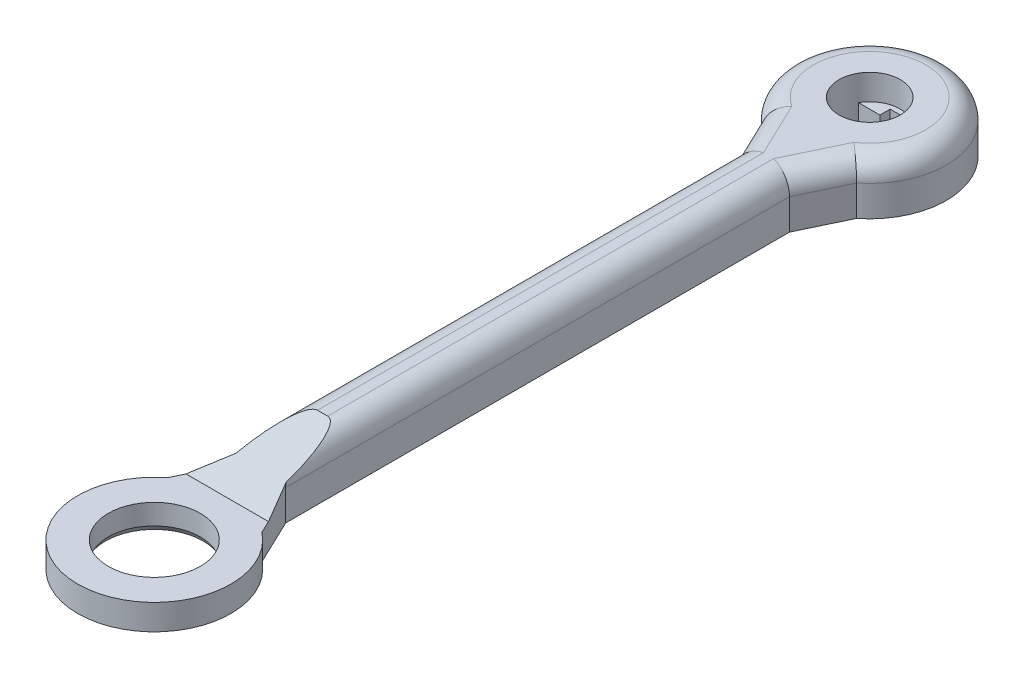
SolidWorks part; units mm, degrees
ref_plane "Front Plane" through (0, 0, 0) normal (0, 0, 1) x (1, 0, 0)
ref_plane "Top Plane" through (0, 0, 0) normal (0, 1, 0) x (1, 0, 0)
ref_plane "Right Plane" through (0, 0, 0) normal (1, 0, 0) x (0, 0, -1)
sketch "Sketch1" plane through (0, 0, 0) normal (0, 1, 0) x (1, 0, 0)
  line L0 (-2.5, 35) -> (-2.5, 0)
  line L1 (-2.5, 35) -> (2.5, 35)
  line L2 (-2.5, 0) -> (2.5, 0)
  line L3 (2.5, 35) -> (2.5, 0)
  line L4 (-2.5, 35) -> (2.5, 0) construction
  line L5 (-2.5, 0) -> (2.5, 35) construction
  circle A0 centre (0, 35) radius 7.5
  point P1 (0, 17.5)
  dimension "D1" = 15
  dimension "D2" = 35
  dimension "D3" = 5
  dimension "D4" = 35
  dimension "D5" = 2.5
extrude "Boss-Extrude1" add sketch "Sketch1" along normal blind 5 contours A0 L0 L2 L3 | L3 A0 L0 L1 | L0 A0 L3 L1 region at (0, 0, -31.3195) region at (0, 0, -35.9678) region at (0, 0, -13.8209)
mirror "Mirror1" about plane through (0, 0, 0) normal (0, 0, 1) of "Boss-Extrude1"
sketch "Sketch2" plane through (0, 0, 0) normal (0, 1, 0) x (1, 0, 0)
  circle A0 centre (0, -35) radius 4.5
  circle A1 centre (0, 35) radius 3
  dimension "D1" = 9
  dimension "D2" = 6
extrude "Cut-Extrude1" cut sketch "Sketch2" along normal blind 5
chamfer "Chamfer3" distance 2 angle 45 4 edges at (-2.5, 2.5, -27.9289) (2.5, 2.5, -27.9289) (-2.5, 2.5, 27.9289) (2.5, 2.5, 27.9289) first distance on face at (0, 2.5, -35.2145) first distance on face at (0, 2.5, 35.2145)
sketch "Sketch4" plane through (0, 5, 0) normal (0, 1, 0) x (1, 0, 0)
  line L1 (8, -27.8664) -> (-8, -27.8664)
  line L2 (8, -27.8664) -> (8, -43.8664)
  line L3 (8, -43.8664) -> (-8, -43.8664)
  line L4 (-8, -27.8664) -> (-8, -43.8664)
  dimension "D1" = 16
  dimension "D2" = 16
  dimension "D3" = 8
  dimension "D4" = 27.8664
extrude "Cut-Extrude2" cut sketch "Sketch4" against normal blind 2.5
fillet "Fillet3" radius 2 5 edges at (-2.5, 5, 0) (2.5, 5, 0) (3.5621, 5, -26.8713) (0, 5, -42.5) (-3.5621, 5, -26.8713)
sketch "Sketch5" plane through (0, 0, 0) normal (0, 1, 0) x (1, 0, 0)
  line L0 (-3, 38) -> (3, 38)
  line L1 (3, 38) -> (3, 36.5)
  line L2 (3, 36.5) -> (0.5, 36.5)
  line L3 (0.5, 36.5) -> (0.5, 37.5)
  line L4 (0.5, 37.5) -> (-0.5, 37.5)
  line L5 (-0.5, 37.5) -> (-0.5, 36.5)
  line L6 (-0.5, 36.5) -> (-3, 36.5)
  line L7 (-3, 36.5) -> (-3, 38)
  circle A0 centre (0, 35) radius 3 construction
  point P2 (0, 38)
  dimension "D1" = 1.5
  dimension "D2" = 1
  dimension "D3" = 1
  dimension "D4" = 6
extrude "Boss-Extrude2" add sketch "Sketch5" along normal blind 2.5
chamfer "Chamfer4" distance 0.5 angle 30 7 edges at (0, 0, 39.5) (0.5, 0, -37) (1.549, 0, -36.5) (0, 0, -37.5) (-0.5, 0, -37) (-1.549, 0, -36.5) (0, 0, -32) first distance on face at (0, 2.5, 30.5) first distance on face at (0.5, 1.25, -37) first distance on face at (1.549, 1.25, -36.5) first distance on face at (0, 1.25, -37.5) first distance on face at (-0.5, 1.25, -37) first distance on face at (-1.549, 1.25, -36.5) first distance on face at (0, 5, -32)
chamfer "Chamfer5" distance 2.5 angle 75 1 edges at (0, 5, 27.8664) first distance on face at (0, 3.75, 27.8664)
